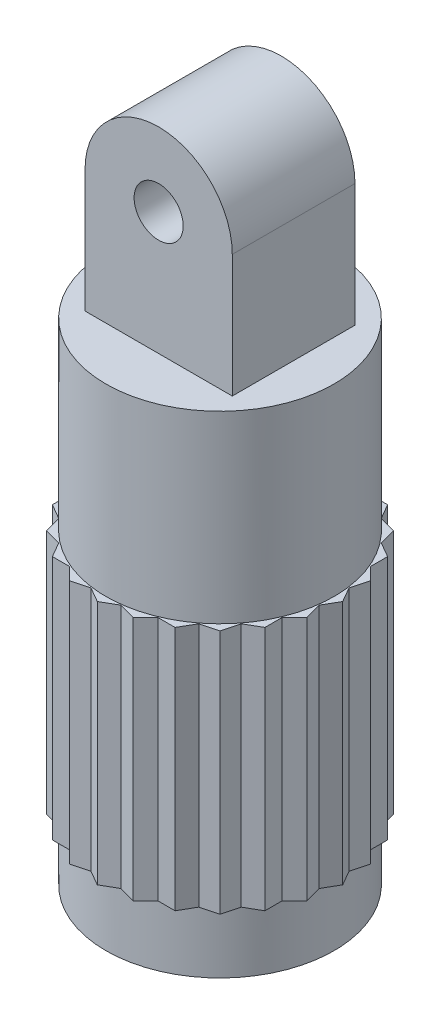
SolidWorks part; units mm, degrees
ref_plane "Front Plane" through (0, 0, 0) normal (0, 0, 1) x (1, 0, 0)
ref_plane "Top Plane" through (0, 0, 0) normal (0, 1, 0) x (1, 0, 0)
ref_plane "Right Plane" through (0, 0, 0) normal (1, 0, 0) x (0, 0, -1)
sketch "Sketch1" plane through (0, 0, 0) normal (0, 0, 1) x (1, 0, 0)
  line L0 (0, 0) -> (0, 112)
  line L1 (-3.9996, 108.0588) -> (-5, 40)
  line L2 (-5, 40) -> (-5, 0)
  line L3 (-5, 0) -> (0, 0)
  arc A0 (0, 112) -> (-3.9996, 108.0588) centre (0, 108) ccw
  dimension "D2" = 4
  dimension "D1" = 112
  dimension "D3" = 5
  dimension "D4" = 40
revolve "Revolve1" [suppressed] add sketch "Sketch1" angle 360 about L0
sketch "Sketch3" plane through (0, 0, 0) normal (0, 1, 0) x (1, 0, 0)
  circle A0 centre (0, 0) radius 4.65
  dimension "D1" = 9.3
extrude "Boss-Extrude1" add sketch "Sketch3" along normal blind 20
sketch "Sketch4" plane through (0, 0, 0) normal (0, 0, 1) x (1, 0, 0)
  line L0 (3, 20) -> (-3, 20)
  line L1 (4.65, 20) -> (-4.65, 20) construction
  line L2 (-3, 20) -> (-3, 25)
  line L3 (-3, 25) -> (3, 25) construction
  line L4 (3, 25) -> (3, 20)
  line L5 (0, 20) -> (0, 25) construction
  arc A0 (3, 25) -> (-3, 25) centre (0, 25) ccw
  circle A1 centre (0, 25) radius 1
  dimension "D2" = 2
  dimension "D1" = 5
  dimension "D3" = 6
extrude "Boss-Extrude2" add sketch "Sketch4" along normal mid plane 5
sketch "Sketch5" plane through (0, 0, 0) normal (0, -1, 0) x (1, 0, 0)
  line L0 (-5, 0) -> (-2.5, -4.3301)
  line L1 (2.5, -4.3301) -> (5, 0)
  line L2 (5, 0) -> (2.5, 4.3301)
  line L3 (2.5, 4.3301) -> (-2.5, 4.3301)
  line L4 (-2.5, 4.3301) -> (-5, 0)
  line L5 (-2.5, -4.3301) -> (2.5, -4.3301)
  circle A0 centre (0, 0) radius 4.3301 construction
  dimension "D1" = 10
extrude "Boss-Extrude3" add sketch "Sketch5" against normal blind 10 from offset 2.5 offset against normal yes
pattern_circular "CirPattern1" count 4 every 15 about axis through (0, 20, 0) along (0, -1, 0) of "Boss-Extrude3"
